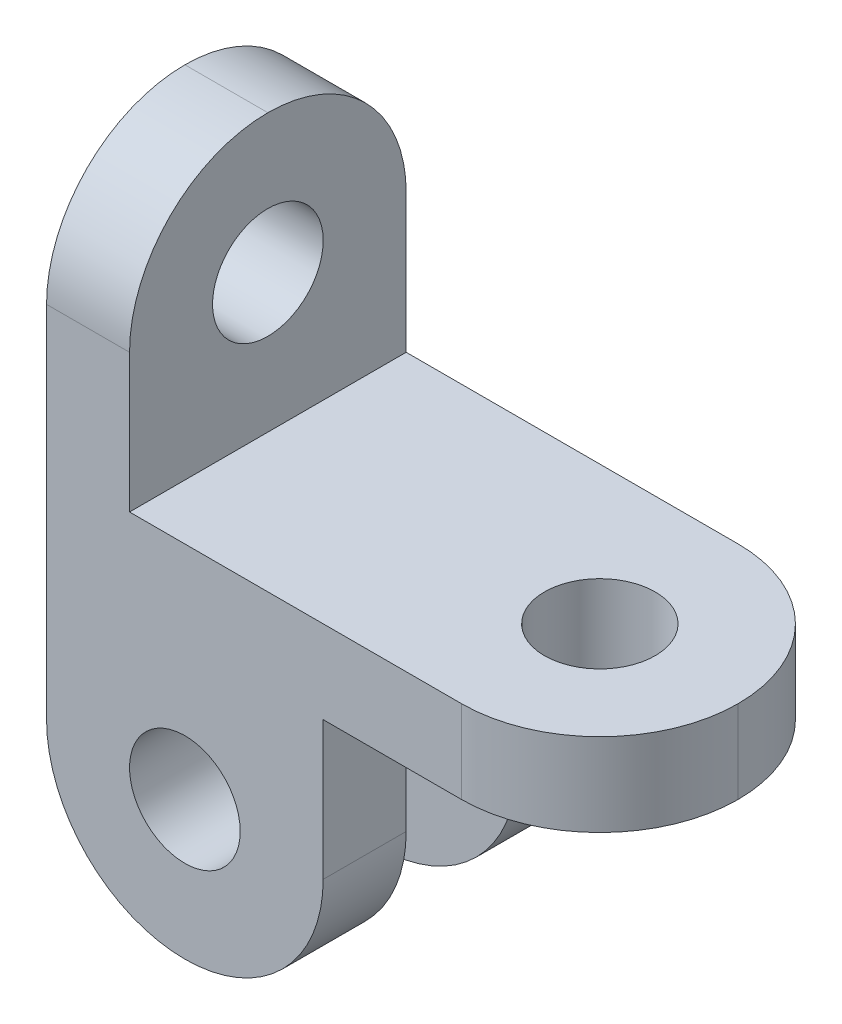
SolidWorks part; units mm, degrees
ref_plane "Front Plane" through (0, 0, 0) normal (0, 0, 1) x (1, 0, 0)
ref_plane "Top Plane" through (0, 0, 0) normal (0, 1, 0) x (1, 0, 0)
ref_plane "Right Plane" through (0, 0, 0) normal (1, 0, 0) x (0, 0, -1)
sketch "Sketch1" plane through (0, 0, 0) normal (0, 1, 0) x (1, 0, 0)
  line L1 (-34.2857, 16.6857) -> (45.7143, 16.6857)
  line L2 (-34.2857, 16.6857) -> (-34.2857, -23.3143)
  line L3 (-34.2857, -23.3143) -> (45.7143, -23.3143)
  line L4 (45.7143, 16.6857) -> (45.7143, -23.3143)
  dimension "D1" = 40
  dimension "D2" = 80
extrude "Boss-Extrude1" add sketch "Sketch1" along normal blind 12
sketch "Sketch2" plane through (0, 12, 0) normal (0, 1, 0) x (1, 0, 0)
  line L0 (-34.2857, -23.3143) -> (45.7143, -23.3143) construction
  line L1 (-34.2857, 16.6857) -> (-22.2857, 16.6857)
  line L2 (-34.2857, 16.6857) -> (-34.2857, -23.3143)
  line L3 (-34.2857, -23.3143) -> (-22.2857, -23.3143)
  line L4 (-22.2857, 16.6857) -> (-22.2857, -23.3143)
  dimension "D1" = 12
extrude "Boss-Extrude2" add sketch "Sketch2" along normal blind 40
sketch "Sketch3" plane through (0, 0, 0) normal (0, -1, 0) x (1, 0, 0)
  line L1 (-34.2857, 23.3143) -> (5.7143, 23.3143)
  line L2 (-34.2857, 23.3143) -> (-34.2857, 11.3143)
  line L3 (-34.2857, 11.3143) -> (5.7143, 11.3143)
  line L4 (5.7143, 23.3143) -> (5.7143, 11.3143)
  line L5 (-34.2857, -16.6857) -> (5.7143, -16.6857)
  line L6 (-34.2857, -16.6857) -> (-34.2857, -4.6857)
  line L7 (-34.2857, -4.6857) -> (5.7143, -4.6857)
  line L8 (5.7143, -16.6857) -> (5.7143, -4.6857)
  dimension "D1" = 40
  dimension "D2" = 40
  dimension "D3" = 12
  dimension "D4" = 12
extrude "Boss-Extrude3" add sketch "Sketch3" along normal blind 40
fillet "Fillet1" radius 20 8 edges at (-34.2857, -40, -10.6857) (-34.2857, -40, 17.3143) (5.7143, -40, -10.6857) (5.7143, -40, 17.3143) (45.7143, 6, -16.6857) (45.7143, 6, 23.3143) (-28.2857, 52, -16.6857) (-28.2857, 52, 23.3143)
sketch "Sketch4" plane through (-22.2857, 0, 0) normal (1, 0, 0) x (0, 0, -1)
  line L0 (16.6857, 32) -> (16.6857, 12) construction
  line L1 (-23.3143, 12) -> (16.6857, 12) construction
  circle A0 centre (-3.3143, 32) radius 8
  point P6 (-3.3143, 12)
  dimension "D1" = 16
  dimension "D2" = 20
  dimension "D3" = 20
extrude "Cut-Extrude1" cut sketch "Sketch4" against normal blind 12
sketch "Sketch5" plane through (0, 12, 0) normal (0, 1, 0) x (1, 0, 0)
  line L0 (-22.2857, -23.3143) -> (25.7143, -23.3143) construction
  line L1 (-22.2857, -23.3143) -> (-22.2857, 16.6857) construction
  circle A0 centre (25.7143, -3.3143) radius 8
  dimension "D2" = 16
  dimension "D1" = 20
  dimension "D3" = 48
extrude "Cut-Extrude2" cut sketch "Sketch5" against normal blind 12
sketch "Sketch6" plane through (0, 0, 23.3143) normal (0, 0, 1) x (1, 0, 0)
  circle A0 centre (-14.2857, -20) radius 8
extrude "Cut-Extrude3" cut sketch "Sketch6" against normal through all
